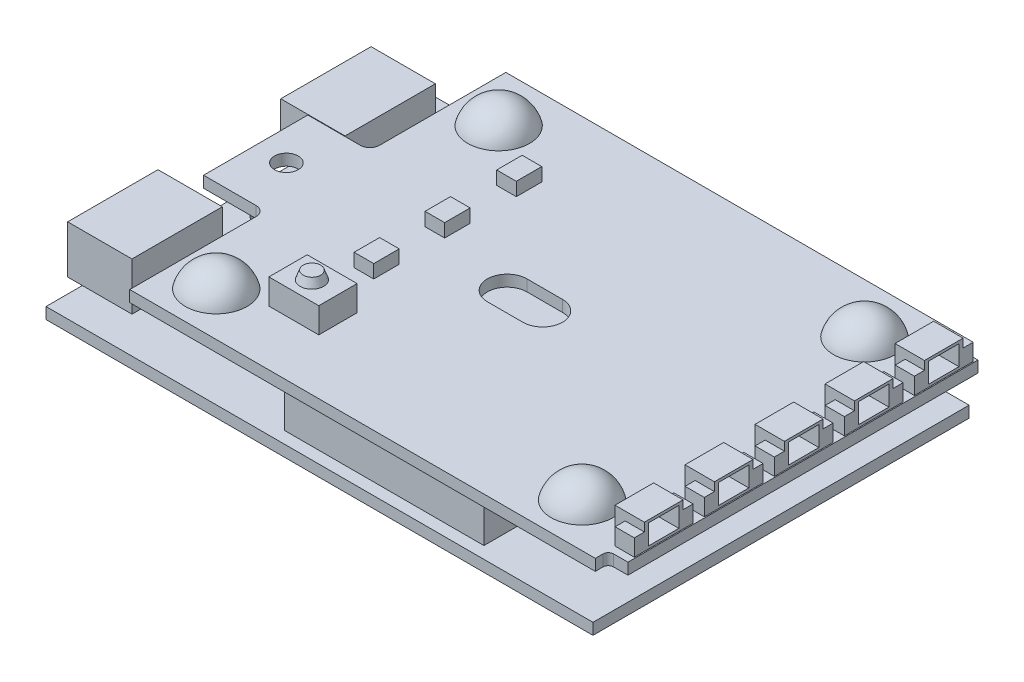
SolidWorks part; units mm, degrees
ref_plane "Front Plane" through (0, 0, 0) normal (0, 0, 1) x (1, 0, 0)
ref_plane "Top Plane" through (0, 0, 0) normal (0, 1, 0) x (1, 0, 0)
ref_plane "Right Plane" through (0, 0, 0) normal (1, 0, 0) x (0, 0, -1)
sketch "Sketch1" plane through (0, 0, 0) normal (0, 1, 0) x (1, 0, 0)
  line L1 (0, 0) -> (77.978, 0)
  line L2 (0, 0) -> (0, -53.6194)
  line L3 (0, -53.6194) -> (77.978, -53.6194)
  line L4 (77.978, 0) -> (77.978, -53.6194)
  dimension "D1" = 77.978
  dimension "D2" = 53.6194
extrude "Bottom Board" add sketch "Sketch1" along normal blind 1.6129
sketch "Sketch2" plane through (0, 1.6129, 0) normal (0, 1, 0) x (-1, 0, 0)
  line L0 (0, 0) -> (0, 53.6194) construction
  line L1 (2.0955, 5.1816) -> (-7.0739, 5.1816)
  line L2 (2.0955, 5.1816) -> (2.0955, 18.0594)
  line L3 (2.0955, 18.0594) -> (-7.0739, 18.0594)
  line L4 (-7.0739, 5.1816) -> (-7.0739, 18.0594)
  line L5 (-77.978, 0) -> (0, 0) construction
  dimension "D1" = 12.8778
  dimension "D2" = 9.1694
  dimension "D3" = 5.1816
  dimension "D4" = 2.0955
extrude "Connector Body" add sketch "Sketch2" along normal blind 6.8199
sketch "Sketch4" plane through (-2.0955, 0, 0) normal (-1, 0, 0) x (0, 0, 1)
  line L0 (5.1816, 8.4328) -> (5.1816, 1.6129) construction
  line L1 (5.7658, 7.8105) -> (8.3947, 7.8105)
  line L2 (5.7658, 7.8105) -> (5.7658, 5.2197)
  line L3 (5.7658, 5.2197) -> (8.3947, 5.2197)
  line L4 (8.3947, 7.8105) -> (8.3947, 5.2197)
  line L5 (5.1816, 8.4328) -> (18.0594, 8.4328) construction
  line L6 (8.7926, 7.8105) -> (8.7926, 5.2197)
  line L7 (8.7926, 5.2197) -> (11.4215, 5.2197)
  line L8 (11.4215, 7.8105) -> (11.4215, 5.2197)
  line L9 (8.7926, 7.8105) -> (11.4215, 7.8105)
  line L10 (11.8195, 7.8105) -> (11.8195, 5.2197)
  line L11 (11.8195, 5.2197) -> (14.4484, 5.2197)
  line L12 (14.4484, 7.8105) -> (14.4484, 5.2197)
  line L13 (11.8195, 7.8105) -> (14.4484, 7.8105)
  line L14 (14.8463, 7.8105) -> (14.8463, 5.2197)
  line L15 (14.8463, 5.2197) -> (17.4752, 5.2197)
  line L16 (17.4752, 7.8105) -> (17.4752, 5.2197)
  line L17 (14.8463, 7.8105) -> (17.4752, 7.8105)
  line L18 (5.7658, 4.826) -> (5.7658, 2.2352)
  line L19 (5.7658, 2.2352) -> (8.3947, 2.2352)
  line L20 (8.3947, 4.826) -> (8.3947, 2.2352)
  line L21 (5.7658, 4.826) -> (8.3947, 4.826)
  line L22 (8.7926, 4.826) -> (8.7926, 2.2352)
  line L23 (8.7926, 2.2352) -> (11.4215, 2.2352)
  line L24 (11.4215, 4.826) -> (11.4215, 2.2352)
  line L25 (8.7926, 4.826) -> (11.4215, 4.826)
  line L26 (11.8195, 4.826) -> (11.8195, 2.2352)
  line L27 (11.8195, 2.2352) -> (14.4484, 2.2352)
  line L28 (14.4484, 4.826) -> (14.4484, 2.2352)
  line L29 (11.8195, 4.826) -> (14.4484, 4.826)
  line L30 (14.8463, 4.826) -> (14.8463, 2.2352)
  line L31 (14.8463, 2.2352) -> (17.4752, 2.2352)
  line L32 (17.4752, 4.826) -> (17.4752, 2.2352)
  line L33 (14.8463, 4.826) -> (17.4752, 4.826)
  line L34 (18.0594, 8.4328) -> (18.0594, 1.6129) construction
  line L35 (17.4752, 7.4085) -> (18.0594, 7.4085) construction
  line L36 (5.7658, 7.5345) -> (5.1816, 7.5345) construction
  line L37 (7.8077, 7.8105) -> (7.8077, 8.4328)
  line L38 (7.8077, 2.2352) -> (7.8077, 1.6129)
  line L39 (5.1816, 1.6129) -> (18.0594, 1.6129) construction
  dimension "D1" = 2.6289
  dimension "D2" = 2.5908
  dimension "D3" = 0.5842
  dimension "D4" = 0.6223
  dimension "D5" = 4
  dimension "D6" = 2
extrude "Connector Holes" cut sketch "Sketch4" against normal blind 5.08 contours L4 L1 L2 L3 | L9 L6 L7 L8 | L13 L10 L11 L12 | L17 L14 L15 L16 | L33 L30 L31 L32 | L29 L26 L27 L28 | L25 L22 L23 L24 | L21 L18 L19 L20 region at (-2.0955, 6.5151, 7.0802) region at (-2.0955, 6.5151, 10.1071) region at (-2.0955, 6.5151, 13.1339) region at (-2.0955, 6.5151, 16.1608) region at (-2.0955, 3.5306, 7.0802) region at (-2.0955, 3.5306, 10.1071) region at (-2.0955, 3.5306, 13.1339) region at (-2.0955, 3.5306, 16.1608)
ref_plane "Center Plane" through (0, 0, 26.8097) normal (0, 0, -1) x (-1, 0, 0)
mirror "Connector Mirror" about plane through (0, 0, 26.8097) normal (0, 0, -1) of "Connector Holes", "Connector Body"
sketch "Sketch5" plane through (0, 1.6129, 0) normal (0, 1, 0) x (1, 0, 0)
  line L0 (77.978, -26.8097) -> (0, -26.8097) construction
  line L1 (77.978, -53.6194) -> (77.978, 0) construction
  line L2 (0, -18.0594) -> (0, -35.56) construction
  line L3 (2.9845, -26.8097) -> (2.9845, -21.4955) construction
  line L4 (36.0172, -26.8097) -> (36.0172, -8.1241) construction
  line L5 (0, -18.0594) -> (0, -35.56) construction
  circle A0 centre (4.68, -26.8097) radius 1.6955
  circle A1 centre (39.0652, -26.8097) radius 3.048
  dimension "D1" = 3.3909
  dimension "D3" = 6.096
  dimension "D2" = 2.9845
  dimension "D4" = 36.0172
extrude "Bottom Board Hole" cut sketch "Sketch5" against normal up to next
sketch "Sketch6" plane through (0, 1.6129, 0) normal (0, 1, 0) x (-1, 0, 0)
  line L0 (-77.978, 0) -> (0, 0) construction
  line L1 (-39.37, 1.7018) -> (-67.818, 1.7018)
  line L2 (-39.37, 1.7018) -> (-39.37, 7.2644)
  line L3 (-39.37, 7.2644) -> (-67.818, 7.2644)
  line L4 (-67.818, 1.7018) -> (-67.818, 7.2644)
  line L5 (-77.978, 53.6194) -> (-77.978, 0) construction
  line L6 (-32.2834, 46.355) -> (-60.7314, 46.355)
  line L7 (-32.2834, 46.355) -> (-32.2834, 51.9176)
  line L8 (-32.2834, 51.9176) -> (-60.7314, 51.9176)
  line L9 (-60.7314, 46.355) -> (-60.7314, 51.9176)
  line L10 (0, 18.0594) -> (0, 35.56) construction
  line L12 (-44.4047, 1.7018) -> (-44.4047, 0) construction
  line L13 (-37.561, 51.9176) -> (-37.561, 53.6194) construction
  line L14 (0, 53.6194) -> (-77.978, 53.6194) construction
  dimension "D1" = 28.448
  dimension "D2" = 5.5626
  dimension "D3" = 1.7018
  dimension "D4" = 10.16
  dimension "D5" = 28.448
  dimension "D6" = 5.5626
  dimension "D7" = 32.2834
extrude "Layer Connectors" add sketch "Sketch6" along normal blind 6.4516
sketch "Sketch7" plane through (0, 8.0645, 0) normal (0, 1, 0) x (1, 0, 0)
  line L0 (77.978, -53.6194) -> (77.978, 0) construction
  line L1 (78.3082, 0) -> (11.938, 0)
  line L2 (81.1022, -1.8542) -> (81.1022, -51.7652)
  line L3 (78.3082, -53.6194) -> (11.938, -53.6194)
  line L4 (11.938, 0) -> (11.938, -18.0086)
  line L5 (0, -18.0594) -> (0, -35.56) construction
  line L6 (77.978, 0) -> (0, 0) construction
  line L7 (0, -53.6194) -> (77.978, -53.6194) construction
  line L8 (15.6034, 0) -> (15.6034, -19.3802) construction
  line L9 (10.5664, -19.3802) -> (3.0861, -19.3802)
  line L10 (11.938, -35.6108) -> (11.938, -53.6194)
  line L11 (10.5664, -34.2392) -> (3.0861, -34.2392)
  line L12 (3.0861, -19.3802) -> (3.0861, -34.2392)
  line L13 (10.5664, -19.3802) -> (15.6034, -19.3802) construction
  line L14 (16.8171, -34.2392) -> (16.8171, -53.6194) construction
  line L15 (10.5664, -34.2392) -> (16.8171, -34.2392) construction
  line L16 (77.978, -26.8097) -> (0, -26.8097) construction
  line L17 (5.7658, -26.8097) -> (5.7658, -22.9762) construction
  line L18 (36.1061, -26.8097) -> (46.8249, -26.8097) construction
  line L19 (38.9318, -23.984) -> (43.9992, -23.984)
  line L20 (36.1061, -26.8097) -> (36.1061, -33.1542) construction
  line L21 (38.9318, -29.6354) -> (43.9992, -29.6355)
  line L22 (78.3082, -53.6194) -> (78.3082, -52.5272)
  line L23 (81.1022, -51.7652) -> (79.0702, -51.7652)
  line L25 (81.1022, -1.8542) -> (79.0702, -1.8542)
  line L26 (78.3082, 0) -> (78.3082, -1.0922)
  arc A0 (11.938, -18.0086) -> (10.5664, -19.3802) centre (10.5664, -18.0086) cw
  arc A1 (10.5664, -34.2392) -> (11.938, -35.6108) centre (10.5664, -35.6108) cw
  circle A2 centre (7.4613, -26.8097) radius 1.6955
  circle A3 centre (4.68, -26.8097) radius 1.6955 construction
  arc A4 (38.9318, -29.6354) -> (38.9318, -23.984) centre (38.9318, -26.8097) cw
  arc A5 (43.9992, -23.984) -> (43.9992, -29.6355) centre (43.9992, -26.8097) cw
  arc A6 (79.0702, -1.8542) -> (78.3082, -1.0922) centre (79.0702, -1.0922) cw
  arc A7 (79.0702, -51.7652) -> (78.3082, -52.5272) centre (79.0702, -52.5272) ccw
  point P45 (78.3082, -1.8542)
  dimension "D5" = 1.3716
  dimension "D6" = 1.3716
  dimension "D13" = 0.762
  dimension "D1" = 3.1242
  dimension "D2" = 11.938
  dimension "D3" = 19.3802
  dimension "D4" = 3.0861
  dimension "D7" = 2.6797
  dimension "D8" = 5.6515
  dimension "D9" = 10.7188
  dimension "D10" = 33.02
  dimension "D11" = 2.794
  dimension "D12" = 1.8542
extrude "Top Board" add sketch "Sketch7" along normal blind 1.6129
sketch "Sketch8" plane through (0, 9.6774, 0) normal (0, 1, 0) x (1, 0, 0)
  line L1 (80.9498, -2.3876) -> (78.2066, -2.3876)
  line L2 (80.9498, -2.3876) -> (80.9498, -10.7696)
  line L3 (80.9498, -10.7696) -> (78.2066, -10.7696)
  line L4 (78.2066, -2.3876) -> (78.2066, -10.7696)
  line L5 (78.3082, 0) -> (11.938, 0) construction
  line L6 (81.1022, -51.7652) -> (81.1022, -1.8542) construction
  dimension "D1" = 2.7432
  dimension "D2" = 8.382
  dimension "D3" = 2.3876
  dimension "D4" = 0.1524
extrude "Maker Connector Sides" add sketch "Sketch8" along normal blind 2.3876
sketch "Sketch9" plane through (0, 12.065, 0) normal (0, 1, 0) x (1, 0, 0)
  line L0 (80.9498, -10.7696) -> (80.9498, -2.3876) construction
  line L1 (80.9498, -3.8227) -> (76.7588, -3.8227)
  line L2 (80.9498, -3.8227) -> (80.9498, -9.3345)
  line L3 (80.9498, -9.3345) -> (76.7588, -9.3345)
  line L4 (76.7588, -3.8227) -> (76.7588, -9.3345)
  line L6 (78.7411, -2.3876) -> (78.7411, -3.8227) construction
  line L7 (80.9498, -2.3876) -> (78.2066, -2.3876) construction
  line L9 (78.7411, -9.3345) -> (78.7411, -10.7696) construction
  line L10 (78.2066, -10.7696) -> (80.9498, -10.7696) construction
  dimension "D1" = 5.5118
  dimension "D2" = 4.191
extrude "Marker Connector Box" add sketch "Sketch9" along normal blind 1.2192
sketch "Sketch10" plane through (0, 9.6774, 0) normal (0, 1, 0) x (1, 0, 0)
  line L0 (76.7588, -9.3345) -> (78.2066, -9.3345) construction
  line L1 (78.2066, -3.8227) -> (76.7588, -3.8227) construction
  line L2 (76.7588, -3.8227) -> (76.7588, -9.3345) construction
  line L3 (76.7588, -9.3345) -> (78.2066, -9.3345)
  line L4 (78.2066, -3.8227) -> (76.7588, -3.8227)
  line L5 (76.7588, -3.8227) -> (76.7588, -9.3345)
  line L10 (78.2066, -3.8227) -> (76.7588, -3.8227)
  line L11 (78.2066, -9.3345) -> (78.2066, -3.8227)
  line L12 (76.7588, -9.3345) -> (78.2066, -9.3345)
  line L13 (76.7588, -3.8227) -> (76.7588, -9.3345)
  line L14 (78.2066, -3.8227) -> (76.7588, -3.8227)
  line L15 (78.2066, -9.3345) -> (78.2066, -3.8227)
  line L16 (76.7588, -9.3345) -> (78.2066, -9.3345)
  line L17 (76.7588, -3.8227) -> (76.7588, -9.3345)
  line M11 (78.2066, -10.7696) -> (78.2066, -2.3876)
  dimension "D1" = 0
extrude "Marker Connector Rear" add sketch "Sketch10" along normal up to body contours L4 L5 L3 M11 region at (77.4827, 9.6774, 6.5786)
sketch "Sketch11" plane through (81.1022, 0, 0) normal (1, 0, 0) x (0, 0, -1)
  line L0 (-9.3345, 13.2842) -> (-9.3345, 12.065) construction
  line L1 (-8.7376, 12.9032) -> (-4.4196, 12.9032)
  line L2 (-8.7376, 12.9032) -> (-8.7376, 10.0584)
  line L3 (-8.7376, 10.0584) -> (-4.4196, 10.0584)
  line L4 (-4.4196, 12.9032) -> (-4.4196, 10.0584)
  line L5 (-8.7376, 11.497) -> (-9.3345, 11.497) construction
  line L6 (-4.4196, 12.3526) -> (-3.8227, 12.3526) construction
  line L7 (-3.8227, 13.2842) -> (-3.8227, 12.065) construction
  line L8 (-9.3345, 13.2842) -> (-3.8227, 13.2842) construction
  line L10 (-7.3098, 10.0584) -> (-7.3098, 9.6774) construction
  line L11 (-51.7652, 9.6774) -> (-1.8542, 9.6774) construction
  line L12 (-7.3098, 13.2842) -> (-7.3098, 12.9032) construction
  dimension "D1" = 0.5969
  dimension "D2" = 0.381
extrude "Marker Connector " cut sketch "Sketch11" against normal blind 3.175
pattern_linear "Maker Connectors Pattern" count 5 spacing 9.9822 along (0, 0, 1) of "Marker Connector Box", "Marker Connector ", "Maker Connector Sides", "Marker Connector Rear"
sketch "Sketch12" plane through (0, 9.6774, 0) normal (0, 1, 0) x (-1, 0, 0)
  line L0 (-13.589, 7.0866) -> (-13.589, -6.6902) construction
  line L1 (-11.938, 0) -> (-11.938, 18.0086) construction
  line L2 (-17.9959, 2.6797) -> (-29.745, 2.6797) construction
  line L3 (-78.3082, 0) -> (-11.938, 0) construction
  circle A0 centre (-17.9959, 7.0866) radius 4.4069
  dimension "D1" = 8.8138
  dimension "D2" = 1.651
  dimension "D3" = 2.6797
extrude "Glue Dome" add sketch "Sketch12" along normal blind 3.4036
fillet "Glue Dome Fillet" radius 4.5415 1 edges at (17.9959, 13.081, 11.4935)
pattern_linear "Glue pattern" count 2 spacing 40.259 along (0, 0, 1) count 2 spacing 52.1462 along (1, 0, 0) of "Glue Dome Fillet", "Glue Dome"
sketch "Sketch13" plane through (0, 9.6774, 0) normal (0, 1, 0) x (-1, 0, 0)
  line L0 (-78.3082, 0) -> (-11.938, 0) construction
  line L1 (-25.2349, 10.9728) -> (-28.0289, 10.9728)
  line L2 (-25.2349, 10.9728) -> (-25.2349, 14.605)
  line L3 (-25.2349, 14.605) -> (-28.0289, 14.605)
  line L4 (-28.0289, 10.9728) -> (-28.0289, 14.605)
  line L5 (-3.0861, 19.3802) -> (-3.0861, 34.2392) construction
  line L7 (-25.2349, 21.1836) -> (-28.0289, 21.1836)
  line L8 (-25.2349, 21.1836) -> (-25.2349, 24.8158)
  line L9 (-25.2349, 24.8158) -> (-28.0289, 24.8158)
  line L10 (-28.0289, 21.1836) -> (-28.0289, 24.8158)
  line L11 (-25.2349, 31.2928) -> (-28.0289, 31.2928)
  line L12 (-25.2349, 31.2928) -> (-25.2349, 34.925)
  line L13 (-25.2349, 34.925) -> (-28.0289, 34.925)
  line L14 (-28.0289, 31.2928) -> (-28.0289, 34.925)
  dimension "D1" = 2.794
  dimension "D2" = 3.6322
  dimension "D3" = 10.9728
  dimension "D4" = 22.1488
  dimension "D5" = 24.8158
  dimension "D6" = 34.925
extrude "LEDs" add sketch "Sketch13" along normal blind 1.905
sketch "Sketch14" plane through (0, 9.6774, 0) normal (0, 1, 0) x (-1, 0, 0)
  line L0 (-11.938, 53.6194) -> (-78.3082, 53.6194) construction
  line L1 (-23.9014, 40.2844) -> (-31.0134, 40.2844)
  line L2 (-23.9014, 40.2844) -> (-23.9014, 45.7454)
  line L3 (-23.9014, 45.7454) -> (-31.0134, 45.7454)
  line L4 (-31.0134, 40.2844) -> (-31.0134, 45.7454)
  line L5 (-81.1022, 51.7652) -> (-81.1022, 1.8542) construction
  dimension "D1" = 7.112
  dimension "D2" = 5.461
  dimension "D3" = 7.874
  dimension "D4" = 50.0888
extrude "IR receiver base" add sketch "Sketch14" along normal blind 3.6068
sketch "Sketch16" plane through (0, 13.2842, 0) normal (0, 1, 0) x (-1, 0, 0)
  line L0 (-27.305, 40.2844) -> (-27.305, 45.7454) construction
  line L3 (-31.0134, 40.2844) -> (-23.9014, 40.2844) construction
  line L4 (-23.9014, 45.7454) -> (-31.0134, 45.7454) construction
  line L5 (-28.9814, 43.0149) -> (-28.9814, 38.6964) construction
  line L6 (-23.9014, 40.2844) -> (-23.9014, 45.7454) construction
  circle A0 centre (-27.305, 43.0149) radius 1.6764
  circle A1 centre (-27.305, 43.0149) radius 1.2446 construction
  dimension "D1" = 3.3528
  dimension "D2" = 2.4892
  dimension "D3" = 5.08
ref_plane "Plane for IR receiver" through (0, 14.4526, 0) normal (0, 1, 0) x (-1, 0, 0)
sketch "Sketch17" plane through (0, 14.4526, 0) normal (0, 1, 0) x (-1, 0, 0)
  circle A0 centre (-27.305, 43.0149) radius 1.2446 construction
  circle A3 centre (-27.305, 43.0149) radius 1.2446
loft "IR receiver" add profiles "Sketch16", "Sketch17" connector at (28.1584, 13.2842, 44.4578) connector at (27.9456, 14.4526, 44.082)
sketch "Sketch18" plane through (0, 0, 0) normal (0, -1, 0) x (1, 0, 0)
  line L0 (0, 53.6194) -> (77.978, 53.6194) construction
  line L1 (15.2908, 49.5554) -> (18.0848, 49.5554)
  line L2 (15.2908, 49.5554) -> (15.2908, 44.5262)
  line L3 (15.2908, 44.5262) -> (18.0848, 44.5262)
  line L4 (18.0848, 49.5554) -> (18.0848, 44.5262)
  line L5 (0, 0) -> (0, 53.6194) construction
  line L6 (15.2908, 42.7228) -> (18.0848, 42.7228)
  line L7 (15.2908, 42.7228) -> (15.2908, 37.6936)
  line L8 (15.2908, 37.6936) -> (18.0848, 37.6936)
  line L9 (18.0848, 42.7228) -> (18.0848, 37.6936)
  line L10 (77.978, 0) -> (0, 0) construction
  line L11 (20.32, 36.0934) -> (23.114, 36.0934)
  line L12 (20.32, 36.0934) -> (20.32, 31.0642)
  line L13 (20.32, 31.0642) -> (23.114, 31.0642)
  line L14 (23.114, 36.0934) -> (23.114, 31.0642)
  dimension "D1" = 2.794
  dimension "D2" = 5.0292
  dimension "D3" = 4.064
  dimension "D4" = 15.2908
  dimension "D5" = 2.794
  dimension "D6" = 5.0292
  dimension "D7" = 37.6936
  dimension "D8" = 2.794
  dimension "D9" = 5.0292
  dimension "D10" = 20.32
  dimension "D11" = 17.526
extrude "Back components" add sketch "Sketch18" along normal blind 2.4892
sketch "Sketch19" plane through (0, 0, 0) normal (0, -1, 0) x (1, 0, 0)
  line L0 (0, 53.6194) -> (77.978, 53.6194) construction
  line L1 (36.3093, 43.5864) -> (38.0873, 43.5864)
  line L2 (36.3093, 43.5864) -> (36.3093, 40.513)
  line L3 (36.3093, 40.513) -> (38.0873, 40.513)
  line L4 (38.0873, 43.5864) -> (38.0873, 40.513)
  line L5 (77.978, 53.6194) -> (77.978, 0) construction
  line L6 (40.3606, 37.338) -> (42.1386, 37.338)
  line L7 (40.3606, 37.338) -> (40.3606, 34.2646)
  line L8 (40.3606, 34.2646) -> (42.1386, 34.2646)
  line L9 (42.1386, 37.338) -> (42.1386, 34.2646)
  line L10 (51.3334, 18.923) -> (53.1114, 18.923)
  line L11 (51.3334, 18.923) -> (51.3334, 15.8496)
  line L12 (51.3334, 15.8496) -> (53.1114, 15.8496)
  line L13 (53.1114, 18.923) -> (53.1114, 15.8496)
  line L14 (77.978, 0) -> (0, 0) construction
  line L15 (34.9758, 15.24) -> (36.7538, 15.24)
  line L16 (34.9758, 15.24) -> (34.9758, 12.1666)
  line L17 (34.9758, 12.1666) -> (36.7538, 12.1666)
  line L18 (36.7538, 15.24) -> (36.7538, 12.1666)
  line L19 (41.3004, 15.24) -> (43.0784, 15.24)
  line L20 (41.3004, 15.24) -> (41.3004, 12.1666)
  line L21 (41.3004, 12.1666) -> (43.0784, 12.1666)
  line L22 (43.0784, 15.24) -> (43.0784, 12.1666)
  line L23 (74.295, 50.7619) -> (76.073, 50.7619)
  line L24 (74.295, 50.7619) -> (74.295, 47.6885)
  line L25 (74.295, 47.6885) -> (76.073, 47.6885)
  line L26 (76.073, 50.7619) -> (76.073, 47.6885)
  line L27 (70.231, 10.287) -> (70.231, 12.065)
  line L28 (70.231, 10.287) -> (73.3044, 10.287)
  line L29 (73.3044, 10.287) -> (73.3044, 12.065)
  line L30 (70.231, 12.065) -> (73.3044, 12.065)
  line L31 (70.231, 6.2484) -> (70.231, 8.0264)
  line L32 (70.231, 6.2484) -> (73.3044, 6.2484)
  line L33 (73.3044, 6.2484) -> (73.3044, 8.0264)
  line L34 (70.231, 8.0264) -> (73.3044, 8.0264)
  line L35 (23.4315, 27.3558) -> (25.2095, 27.3558)
  line L36 (23.4315, 27.3558) -> (23.4315, 24.2824)
  line L37 (23.4315, 24.2824) -> (25.2095, 24.2824)
  line L38 (25.2095, 27.3558) -> (25.2095, 24.2824)
  line L39 (16.9799, 12.0904) -> (18.7579, 12.0904)
  line L40 (16.9799, 12.0904) -> (16.9799, 9.017)
  line L41 (16.9799, 9.017) -> (18.7579, 9.017)
  line L42 (18.7579, 12.0904) -> (18.7579, 9.017)
  line L43 (0, 0) -> (0, 53.6194) construction
  dimension "D1" = 1.778
  dimension "D2" = 3.0734
  dimension "D3" = 10.033
  dimension "D4" = 39.8907
  dimension "D5" = 1.778
  dimension "D6" = 16.2814
  dimension "D7" = 35.8394
  dimension "D8" = 18.923
  dimension "D9" = 26.6446
  dimension "D10" = 43.0022
  dimension "D11" = 15.24
  dimension "D12" = 36.6776
  dimension "D13" = 5.9309
  dimension "D14" = 3.683
  dimension "D15" = 12.065
  dimension "D16" = 7.747
  dimension "D17" = 8.0264
  dimension "D18" = 27.3558
  dimension "D19" = 25.2095
  dimension "D20" = 18.7579
  dimension "D21" = 12.0904
extrude "Bottom caps" add sketch "Sketch19" along normal blind 1.7526
sketch "Sketch20" plane through (0, 0, 0) normal (0, -1, 0) x (1, 0, 0)
  line L0 (77.978, 0) -> (0, 0) construction
  line L1 (26.924, 6.477) -> (31.8516, 6.477)
  line L2 (26.924, 6.477) -> (26.924, 2.6162)
  line L3 (26.924, 2.6162) -> (31.8516, 2.6162)
  line L4 (31.8516, 6.477) -> (31.8516, 2.6162)
  line L5 (0, 0) -> (0, 53.6194) construction
  dimension "D1" = 4.9276
  dimension "D2" = 3.8608
  dimension "D3" = 6.477
  dimension "D4" = 31.8516
extrude "Chip" add sketch "Sketch20" along normal blind 1.5875
sketch "Sketch21" plane through (0, 0, 0) normal (0, -1, 0) x (1, 0, 0)
  line L0 (77.978, 0) -> (0, 0) construction
  line L1 (54.102, 12.0777) -> (55.5498, 12.0777)
  line L2 (54.102, 12.0777) -> (54.102, 10.0203)
  line L3 (54.102, 10.0203) -> (55.5498, 10.0203)
  line L4 (55.5498, 12.0777) -> (55.5498, 10.0203)
  line L5 (77.978, 53.6194) -> (77.978, 0) construction
  line L6 (57.3278, 12.0777) -> (58.7756, 12.0777)
  line L7 (57.3278, 12.0777) -> (57.3278, 10.0203)
  line L8 (57.3278, 10.0203) -> (58.7756, 10.0203)
  line L9 (58.7756, 12.0777) -> (58.7756, 10.0203)
  dimension "D1" = 1.4478
  dimension "D2" = 2.0574
  dimension "D3" = 12.0777
  dimension "D4" = 23.876
  dimension "D5" = 20.6502
extrude "FLs" add sketch "Sketch21" along normal blind 0.9779
